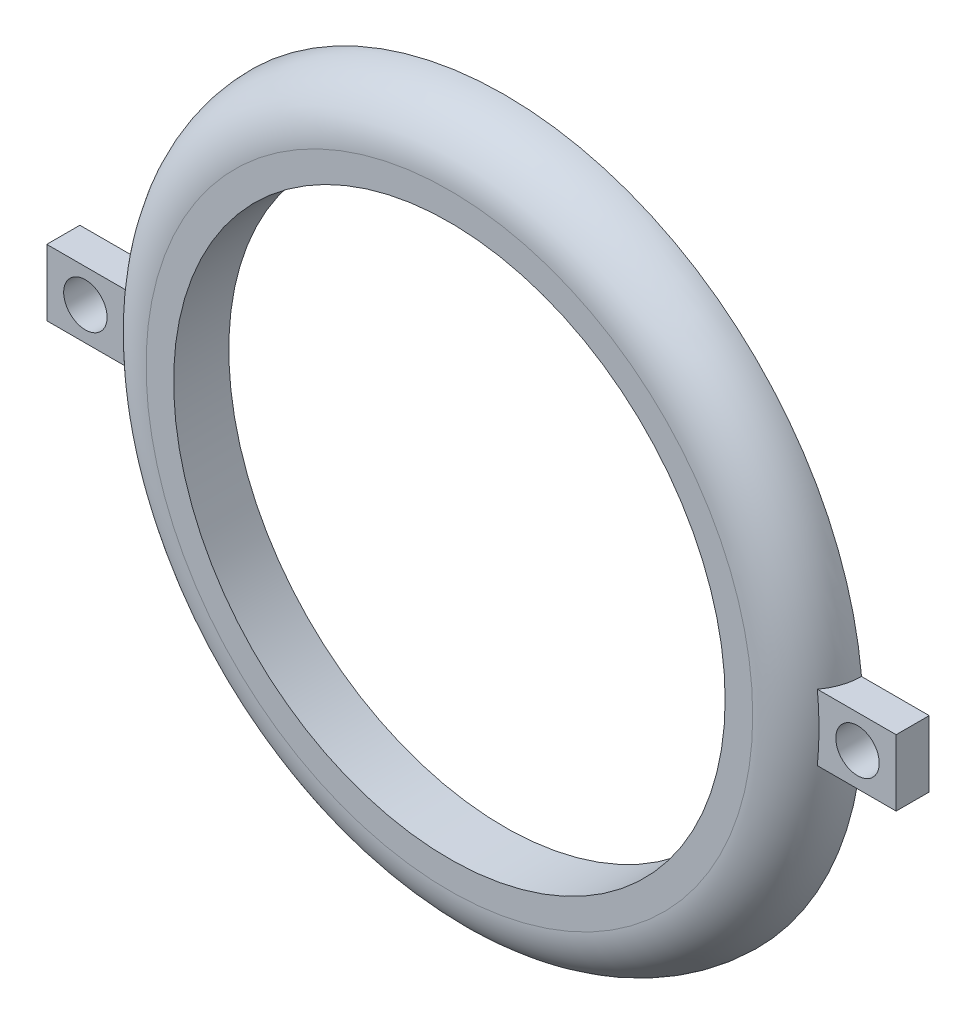
SolidWorks part; units mm, degrees
ref_plane "Front Plane" through (0, 0, 0) normal (0, 0, 1) x (1, 0, 0)
ref_plane "Top Plane" through (0, 0, 0) normal (0, 1, 0) x (1, 0, 0)
ref_plane "Right Plane" through (0, 0, 0) normal (1, 0, 0) x (0, 0, -1)
sketch "Sketch1" plane through (0, 0, 0) normal (0, 0, 1) x (1, 0, 0)
  circle A0 centre (0, 0) radius 16.51
  circle A1 centre (0, 0) radius 12.7
  dimension "D1" = 33.02
  dimension "D2" = 25.4
extrude "Boss-Extrude1" add sketch "Sketch1" along normal blind 2.54
ref_plane "Plane1" through (-16.51, 0, 0) normal (-1, 0, 0) x (0, 0, 1)
sketch "Sketch4" plane through (-16.51, 0, 0) normal (-1, 0, 0) x (0, 0, 1)
  line L0 (0, -1.524) -> (0, 1.524)
  line L1 (0, 16.51) -> (0, -16.51) construction
  line L2 (0, 1.524) -> (1.524, 1.524)
  line L3 (1.524, 1.524) -> (1.524, -1.524)
  line L4 (1.524, -1.524) -> (0, -1.524)
  point P5 (0, 0)
  dimension "D1" = 1.524
  dimension "D2" = 3.048
extrude "Boss-Extrude2" add sketch "Sketch4" against normal up to surface and the other way blind 3.048 up to face at (16.51, 0, 2.54)
mirror "Mirror2" about plane through (0, 0, 0) normal (1, 0, 0) of "Boss-Extrude2"
fillet "Fillet3" radius 2.54 1 edges at (16.51, 0, 2.54)
sketch "Sketch5" plane through (0, 0, 1.524) normal (0, 0, 1) x (1, 0, 0)
  circle A0 centre (-17.78, 0) radius 1
  circle A1 centre (0, 0) radius 17.78 construction
  dimension "D1" = 2
  dimension "D2" = 35.56
extrude "Cut-Extrude1" cut sketch "Sketch5" against normal blind 2.54
mirror "Mirror3" about plane through (0, 0, 0) normal (1, 0, 0) of "Cut-Extrude1"
